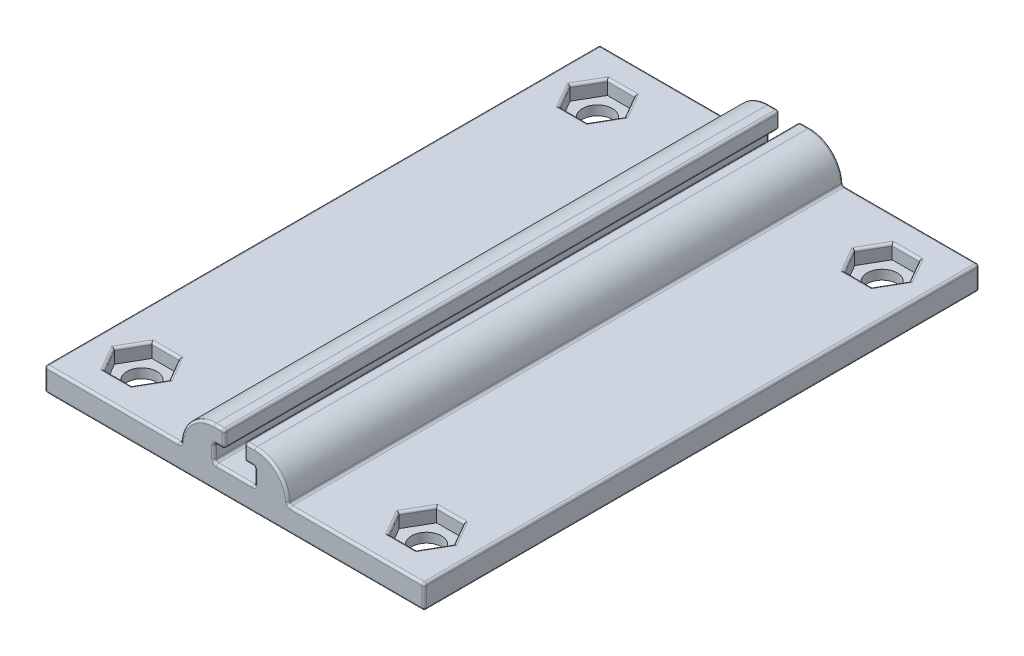
SolidWorks part; units mm, degrees
ref_plane "Front Plane" through (0, 0, 0) normal (0, 0, 1) x (1, 0, 0)
ref_plane "Top Plane" through (0, 0, 0) normal (0, 1, 0) x (1, 0, 0)
ref_plane "Right Plane" through (0, 0, 0) normal (1, 0, 0) x (0, 0, -1)
sketch "Sketch1" plane through (0, 0, 0) normal (0, 0, 1) x (1, 0, 0)
  line L0 (0, -28.2286) -> (0, 28.2286) construction
  line L1 (-40, -2.5) -> (40, -2.5)
  line L2 (-40, -2.5) -> (-40, 2.5)
  line L3 (-40, 2.5) -> (-11.3, 2.5)
  line L4 (40, -2.5) -> (40, 2.5)
  line L5 (-40, -2.5) -> (40, 2.5) construction
  line L6 (-40, 2.5) -> (40, -2.5) construction
  line L7 (-4.3, 2.5) -> (4.3, 2.5)
  line L8 (0.2, 2.5) -> (-4.3, 2.5) construction
  line L9 (0.2, 2.5) -> (0.2, 6) construction
  line L10 (0.2, 6) -> (-4.3, 6) construction
  line L12 (0.2, 6) -> (-2.1, 6) construction
  line L13 (0.2, 6) -> (0.2, 16.858) construction
  line L14 (0.2, 16.858) -> (-2.1, 16.858) construction
  line L15 (-2.1, 6) -> (-2.1, 16.858) construction
  line L16 (-4.3, 6) -> (-2.1, 6)
  line L17 (-4.3, 2.5) -> (-4.3, 6)
  line L18 (-4.3, 9.5) -> (-2.1, 9.5)
  line L19 (-2.1, 6) -> (-2.1, 9.5)
  line L20 (4.3, 2.5) -> (4.3, 6)
  line L21 (2.1, 6) -> (2.1, 9.5)
  line L22 (4.3, 6) -> (2.1, 6)
  line L23 (4.3, 9.5) -> (2.1, 9.5)
  line L24 (11.3, 2.5) -> (40, 2.5)
  arc A0 (-4.3, 9.5) -> (-11.3, 2.5) centre (-4.3, 2.5) ccw
  arc A1 (4.3, 9.5) -> (11.3, 2.5) centre (4.3, 2.5) cw
  point P0 (0, 0)
  point P9 (0, 0)
  dimension "D1" = 80
  dimension "D2" = 5
  dimension "D3" = 3.5
  dimension "D4" = 4.5
  dimension "D5" = 2.3
  dimension "D6" = 3.5
  dimension "D7" = 4.3
  dimension "D8" = 4.2
extrude "Boss-Extrude1" add sketch "Sketch1" along normal blind 58.5 and the other way blind 58.5 contours L7 L20 L22 L21 L23 A1 L24 L4 L1 L2 L3 A0 L18 L19 L16 L17
sketch "Sketch2" plane through (0, -2.5, 0) normal (0, -1, 0) x (1, 0, 0)
  line L0 (0, -58.5) -> (0, -52) construction
  line L2 (-40, -58.5) -> (40, -58.5) construction
  line L3 (0, 58.5) -> (0, 48) construction
  line L4 (-40, 58.5) -> (40, 58.5) construction
  line L5 (0, 48) -> (-30, 48) construction
  circle A0 centre (-30, 48) radius 3.15
  circle A1 centre (30, 48) radius 3.15
  circle A2 centre (30, -48) radius 3.15
  circle A3 centre (-30, -48) radius 3.15
  point P6 (0, 0)
  dimension "D4" = 6.3
  dimension "D1" = 10.5
  dimension "D2" = 6.5
  dimension "D3" = 30
  dimension "D5" = 2
  dimension "D6" = 2
extrude "Cut-Extrude1" cut sketch "Sketch2" against normal blind 58.5
fillet "Fillet1" radius 0.5 50 edges at (40, -2.5, 0) (-40, -2.5, 0) (-4.3, 6, 0) (-2.1, 6, 0) (-2.1, 9.5, 0) (2.1, 9.5, 0) (2.1, 6, 0) (4.3, 6, 0) (4.3, 2.5, 0) (-4.3, 2.5, 0) (-3.2, 6, -58.5) (-2.1, 7.75, -58.5) (-3.2, 9.5, -58.5) (-9.2497, 7.4497, -58.5) (-40, 0, -58.5) (0, -2.5, -58.5) (40, 0, -58.5) (9.2497, 7.4497, -58.5) (3.2, 9.5, -58.5) (2.1, 7.75, -58.5) (3.2, 6, -58.5) (4.3, 4.25, -58.5) (0, 2.5, -58.5) (-4.3, 4.25, -58.5) (0, 2.5, 58.5) (4.3, 4.25, 58.5) (3.2, 6, 58.5) (2.1, 7.75, 58.5) (3.2, 9.5, 58.5) (9.2497, 7.4497, 58.5) (40, 0, 58.5) (0, -2.5, 58.5) (-40, 0, 58.5) (-9.2497, 7.4497, 58.5) (-3.2, 9.5, 58.5) (-2.1, 7.75, 58.5) (-3.2, 6, 58.5) (-4.3, 4.25, 58.5) (-25.65, 2.5, -58.5) (-11.3, 2.5, 0) (-25.65, 2.5, 58.5) (-40, 2.5, 0) (-26.85, 2.5, -48) (-26.85, 2.5, 48) (25.65, 2.5, -58.5) (40, 2.5, 0) (25.65, 2.5, 58.5) (11.3, 2.5, 0) (33.15, 2.5, 48) (33.15, 2.5, -48)
sketch "Sketch3" plane through (0, 2.5, 0) normal (0, 1, 0) x (1, 0, 0)
  line L1 (-24.2265, 48) -> (-27.1132, 53)
  line L2 (-27.1132, 53) -> (-32.8868, 53)
  line L3 (-32.8868, 53) -> (-35.7735, 48)
  line L4 (-35.7735, 48) -> (-32.8868, 43)
  line L5 (-32.8868, 43) -> (-27.1132, 43)
  line L6 (-27.1132, 43) -> (-24.2265, 48)
  line L7 (-24.2265, -48) -> (-27.1132, -43)
  line L8 (-27.1132, -43) -> (-32.8868, -43)
  line L9 (-32.8868, -43) -> (-35.7735, -48)
  line L10 (-35.7735, -48) -> (-32.8868, -53)
  line L11 (-32.8868, -53) -> (-27.1132, -53)
  line L12 (-27.1132, -53) -> (-24.2265, -48)
  circle A0 centre (-30, 48) radius 5 construction
  circle A1 centre (-30, -48) radius 5 construction
  dimension "D1" = 10
  dimension "D2" = 10
extrude "Cut-Extrude2" cut sketch "Sketch3" against normal blind 3
pattern_linear "LPattern1" count 2 spacing 60 along (1, 0, 0) of "Cut-Extrude2"
fillet "Fillet2" radius 0.5 24 edges at (30, 2.5, 43) (25.6699, 2.5, 45.5) (25.6699, 2.5, 50.5) (30, 2.5, 53) (34.3301, 2.5, 50.5) (34.3301, 2.5, 45.5) (30, 2.5, -53) (25.6699, 2.5, -50.5) (25.6699, 2.5, -45.5) (30, 2.5, -43) (34.3301, 2.5, -45.5) (34.3301, 2.5, -50.5) (-30, 2.5, 43) (-34.3301, 2.5, 45.5) (-34.3301, 2.5, 50.5) (-30, 2.5, 53) (-25.6699, 2.5, 50.5) (-25.6699, 2.5, 45.5) (-30, 2.5, -53) (-34.3301, 2.5, -50.5) (-34.3301, 2.5, -45.5) (-30, 2.5, -43) (-25.6699, 2.5, -45.5) (-25.6699, 2.5, -50.5)
